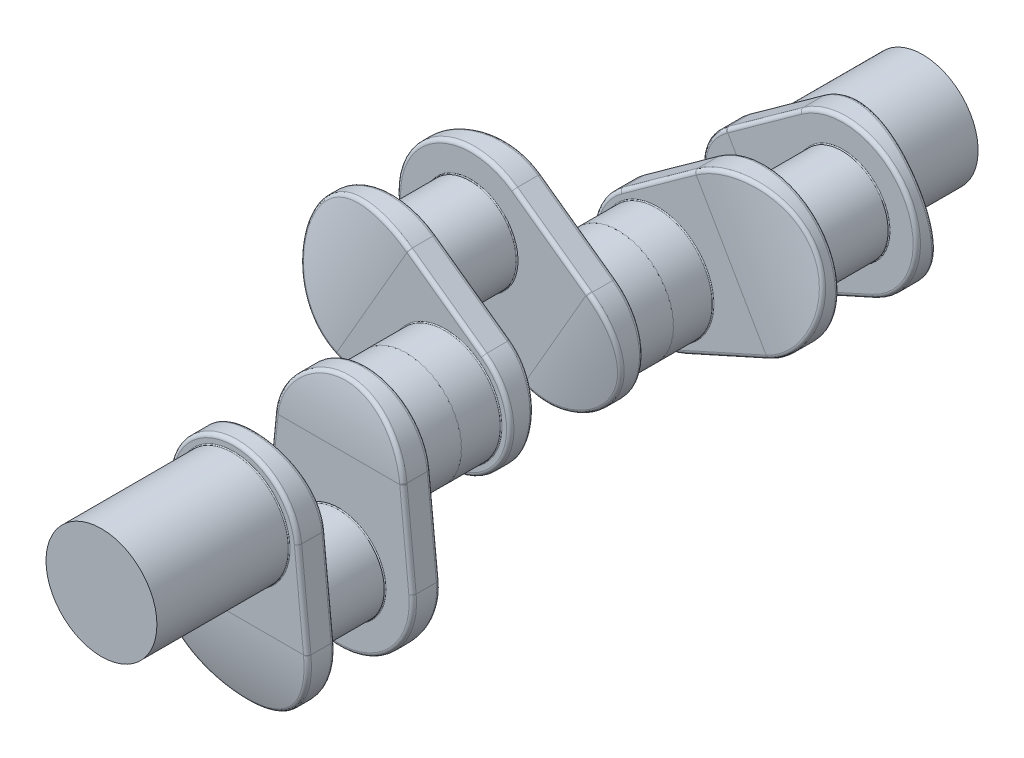
SolidWorks part; units mm, degrees
ref_plane "Front Plane" through (0, 0, 0) normal (0, 0, 1) x (1, 0, 0)
ref_plane "Top Plane" through (0, 0, 0) normal (0, 1, 0) x (1, 0, 0)
ref_plane "Right Plane" through (0, 0, 0) normal (1, 0, 0) x (0, 0, -1)
sketch "Sketch1" plane through (0, 0, 0) normal (0, 0, 1) x (1, 0, 0)
  circle A0 centre (0, 0) radius 38.1
  dimension "D1" = 76.2
extrude "Boss-Extrude1" add sketch "Sketch1" along normal blind 27.31
sketch "Sketch2" plane through (0, 0, 0) normal (0, 0, -1) x (-1, 0, 0)
  line L0 (44.2272, 4.445) -> (50.5454, -58.42)
  line L1 (-44.2272, 4.445) -> (-50.5454, -58.42)
  arc A0 (44.2272, 4.445) -> (-44.2272, 4.445) centre (0, 0) ccw
  arc A1 (-50.5454, -58.42) -> (50.5454, -58.42) centre (0, -63.5) ccw
  dimension "D1" = 88.9
  dimension "D2" = 101.6
  dimension "D3" = 63.5
extrude "Boss-Extrude2" add sketch "Sketch2" along normal blind 19 contours L1 A1 L0 A0
sketch "Sketch3" plane through (0, 0, -19) normal (0, 0, -1) x (-1, 0, 0)
  circle A0 centre (0, -63.5) radius 31.75
  dimension "D1" = 63.5
extrude "Boss-Extrude3" add sketch "Sketch3" along normal blind 26.67
sketch "Sketch4" plane through (0, 0, 0) normal (1, 0, 0) x (0, 0, -1)
  line L0 (14, 44.45) -> (19, 44.45)
  line L1 (19, 44.45) -> (0, 44.45) construction
  line L2 (19, 44.45) -> (19, 3.6456)
  line L3 (19, 4.445) -> (19, -58.42) construction
  line L4 (0, -58.4363) -> (0, -114.3)
  line L5 (0, 4.445) -> (0, -58.42) construction
  line L6 (0, -114.3) -> (9.5, -114.3)
  line L7 (0, -114.3) -> (19, -114.3) construction
  arc A1 (14, 44.45) -> (19, 3.6456) centre (-150, 3.6456) cw
  arc A2 (9.5, -114.3) -> (0, -58.4363) centre (169, -58.4363) cw
  dimension "D2" = 169
  dimension "D3" = 169
  dimension "D1" = 5
extrude "Cut-Extrude1" cut sketch "Sketch4" against normal through all both and the other way through all
fillet "Fillet1" radius 0.64 2 edges at (38.1, 0, 0) (-31.75, -63.5, -19)
fillet "Fillet2" radius 2.54 12 edges at (44.2674, 4.0453, -18.9995) (47.4264, -27.3872, -19) (0, -114.3, -19) (-47.4264, -27.3872, -19) (-44.2674, 4.0453, -18.9995) (-47.3863, -26.9875, 0) (-50.5462, -58.4282, 0) (0.2541, -114.2994, -9.4998) (50.5462, -58.4282, 0) (47.3863, -26.9875, 0) (5.8295, 44.0661, -14.095) (0, 44.45, 0)
mirror "Mirror1" about plane through (0, -63.5, -45.67) normal (0, 0, -1) of bodies 104
ref_axis "Axis1" through (0, 0, 80.2973) along (0, 0, -1)
pattern_linear "LPattern1" count 3 spacing 145.62 along (0, 0, -1) of bodies 105
move or copy body "Body-Move/Copy1" bodies to move or copy 106 copy no rotation origin (0, 0, 0) rotation axis (0, 0, -1) rotation angle 120
move or copy body "Body-Move/Copy2" bodies to move or copy 107 copy no rotation origin (0, 0, 0) rotation axis (0, 0, 1) rotation angle 120
sketch "Sketch5" plane through (0, 0, -409.89) normal (0, 0, -1) x (-1, 0, 0)
  circle A1 centre (0, 0) radius 38.1
  circle A2 centre (0, 0) radius 38.1
  dimension "D1" = 0
extrude "Boss-Extrude4" add sketch "Sketch5" along normal blind 63.5
sketch "Sketch6" plane through (0, 0, 27.31) normal (0, 0, 1) x (1, 0, 0)
  circle A1 centre (0, 0) radius 38.1
  circle A2 centre (0, 0) radius 38.1
  dimension "D1" = 0
extrude "Boss-Extrude5" add sketch "Sketch6" along normal blind 63.5
